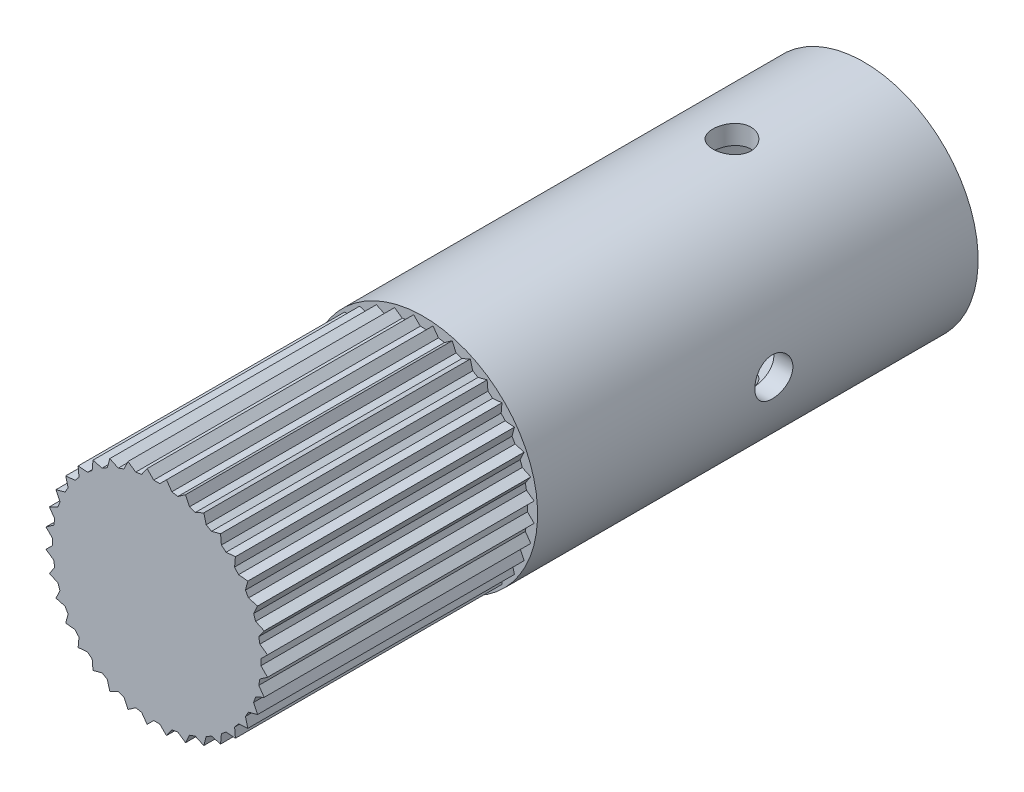
SolidWorks part; units mm, degrees
material "AISI 1015 Steel, Cold Drawn (SS)"
ref_plane "X-Y Datum" through (0, 0, 0) normal (0, 0, 1) x (1, 0, 0)
ref_plane "X-Z Datum" through (0, 0, 0) normal (0, 1, 0) x (1, 0, 0)
ref_plane "Y-Z Datum" through (0, 0, 0) normal (1, 0, 0) x (0, 0, -1)
sketch "Sketch9" plane through (0, 0, 0) normal (0, 1, 0) x (1, 0, 0)
  line L0 (16.002, 0) -> (0, 0)
  line L1 (0, 0) -> (0, -389.0916)
  line L2 (0, -389.0916) -> (-72.2493, -524.9728)
  dimension "D1" = 153.895
  dimension "D2" = 28
  dimension "D3" = 389.0916
  dimension "D5" = 16.002
sketch "Sketch5" plane through (0, 0, 0) normal (0, 1, 0) x (1, 0, 0)
  line L0 (7.9375, -81.1166) -> (7.9375, -22.1615)
  line L1 (7.9375, -22.1615) -> (9.525, -22.1615)
  line L2 (9.525, -22.1615) -> (9.525, -81.1166)
  line L3 (9.525, -81.1166) -> (7.9375, -81.1166)
  line L5 (16.002, 0) -> (0, 0) construction
  line L6 (0, 0) -> (0, -389.0916) construction
  line L7 (0, -389.0916) -> (9.525, -389.0916) construction
  line L8 (12.5602, -61.8666) -> (0, -61.8666) construction
  dimension "D1" = 1.5875
  dimension "D2" = 22.1615
  dimension "D3" = 7.9375
  dimension "D4" = 327.225
  dimension "D5" = 307.975
revolve "Revolve2" add sketch "Sketch5" angle 360 about L1
sketch "Sketch6" plane through (0, 0, 0) normal (0, 1, 0) x (1, 0, 0)
  circle A0 centre (0, -33.1635) radius 1.5875 construction
  circle A1 centre (0, -33.1635) radius 1.5875
sketch "Sketch7" plane through (0, 0, 0) normal (1, 0, 0) x (0, 0, -1)
  circle A2 centre (-39.196, 0) radius 1.5875
  circle A4 centre (-39.196, 0) radius 1.5875 construction
extrude "Cut-Extrude5" cut sketch "Sketch7" against normal through all both and the other way through all
extrude "Cut-Extrude6" cut sketch "Sketch6" against normal through all both and the other way through all
sketch "Sketch8" plane through (0, 0, 0) normal (0, 0, 1) x (1, 0, 0)
  line L0 (9.2357, -0.808) -> (8.6817, -0.254)
  line L1 (8.6817, -0.254) -> (8.6817, 0.254)
  line L2 (8.6817, 0.254) -> (9.2357, 0.808)
  line L3 (8.6817, 0) -> (0, 0) construction
  line L4 (8.9551, -2.3995) -> (8.5057, -1.7577)
  line L5 (8.5057, -1.7577) -> (8.5939, -1.2574)
  line L6 (8.5939, -1.2574) -> (9.2357, -0.808)
  line L7 (8.4024, -3.9181) -> (8.0713, -3.208)
  line L8 (8.0713, -3.208) -> (8.245, -2.7306)
  line L9 (8.245, -2.7306) -> (8.9551, -2.3995)
  line L10 (7.5944, -5.3176) -> (7.3916, -4.5608)
  line L11 (7.3916, -4.5608) -> (7.6456, -4.1209)
  line L12 (7.6456, -4.1209) -> (8.4024, -3.9181)
  line L13 (6.5556, -6.5556) -> (6.4873, -5.7751)
  line L14 (6.4873, -5.7751) -> (6.8138, -5.3859)
  line L15 (6.8138, -5.3859) -> (7.5944, -5.3176)
  line L16 (5.3176, -7.5944) -> (5.3859, -6.8138)
  line L17 (5.3859, -6.8138) -> (5.7751, -6.4873)
  line L18 (5.7751, -6.4873) -> (6.5556, -6.5556)
  line L19 (3.9181, -8.4024) -> (4.1209, -7.6456)
  line L20 (4.1209, -7.6456) -> (4.5608, -7.3916)
  line L21 (4.5608, -7.3916) -> (5.3176, -7.5944)
  line L22 (2.3995, -8.9551) -> (2.7306, -8.245)
  line L23 (2.7306, -8.245) -> (3.208, -8.0713)
  line L24 (3.208, -8.0713) -> (3.9181, -8.4024)
  line L25 (0.808, -9.2357) -> (1.2574, -8.5939)
  line L26 (1.2574, -8.5939) -> (1.7577, -8.5057)
  line L27 (1.7577, -8.5057) -> (2.3995, -8.9551)
  line L28 (-0.808, -9.2357) -> (-0.254, -8.6817)
  line L29 (-0.254, -8.6817) -> (0.254, -8.6817)
  line L30 (0.254, -8.6817) -> (0.808, -9.2357)
  line L31 (-2.3995, -8.9551) -> (-1.7577, -8.5057)
  line L32 (-1.7577, -8.5057) -> (-1.2574, -8.5939)
  line L33 (-1.2574, -8.5939) -> (-0.808, -9.2357)
  line L34 (-3.9181, -8.4024) -> (-3.208, -8.0713)
  line L35 (-3.208, -8.0713) -> (-2.7306, -8.245)
  line L36 (-2.7306, -8.245) -> (-2.3995, -8.9551)
  line L37 (-5.3176, -7.5944) -> (-4.5608, -7.3916)
  line L38 (-4.5608, -7.3916) -> (-4.1209, -7.6456)
  line L39 (-4.1209, -7.6456) -> (-3.9181, -8.4024)
  line L40 (-6.5556, -6.5556) -> (-5.7751, -6.4873)
  line L41 (-5.7751, -6.4873) -> (-5.3859, -6.8138)
  line L42 (-5.3859, -6.8138) -> (-5.3176, -7.5944)
  line L43 (-7.5944, -5.3176) -> (-6.8138, -5.3859)
  line L44 (-6.8138, -5.3859) -> (-6.4873, -5.7751)
  line L45 (-6.4873, -5.7751) -> (-6.5556, -6.5556)
  line L46 (-8.4024, -3.9181) -> (-7.6456, -4.1209)
  line L47 (-7.6456, -4.1209) -> (-7.3916, -4.5608)
  line L48 (-7.3916, -4.5608) -> (-7.5944, -5.3176)
  line L49 (-8.9551, -2.3995) -> (-8.245, -2.7306)
  line L50 (-8.245, -2.7306) -> (-8.0713, -3.208)
  line L51 (-8.0713, -3.208) -> (-8.4024, -3.9181)
  line L52 (-9.2357, -0.808) -> (-8.5939, -1.2574)
  line L53 (-8.5939, -1.2574) -> (-8.5057, -1.7577)
  line L54 (-8.5057, -1.7577) -> (-8.9551, -2.3995)
  line L55 (-9.2357, 0.808) -> (-8.6817, 0.254)
  line L56 (-8.6817, 0.254) -> (-8.6817, -0.254)
  line L57 (-8.6817, -0.254) -> (-9.2357, -0.808)
  line L58 (-8.9551, 2.3995) -> (-8.5057, 1.7577)
  line L59 (-8.5057, 1.7577) -> (-8.5939, 1.2574)
  line L60 (-8.5939, 1.2574) -> (-9.2357, 0.808)
  line L61 (-8.4024, 3.9181) -> (-8.0713, 3.208)
  line L62 (-8.0713, 3.208) -> (-8.245, 2.7306)
  line L63 (-8.245, 2.7306) -> (-8.9551, 2.3995)
  line L64 (-7.5944, 5.3176) -> (-7.3916, 4.5608)
  line L65 (-7.3916, 4.5608) -> (-7.6456, 4.1209)
  line L66 (-7.6456, 4.1209) -> (-8.4024, 3.9181)
  line L67 (-6.5556, 6.5556) -> (-6.4873, 5.7751)
  line L68 (-6.4873, 5.7751) -> (-6.8138, 5.3859)
  line L69 (-6.8138, 5.3859) -> (-7.5944, 5.3176)
  line L70 (-5.3176, 7.5944) -> (-5.3859, 6.8138)
  line L71 (-5.3859, 6.8138) -> (-5.7751, 6.4873)
  line L72 (-5.7751, 6.4873) -> (-6.5556, 6.5556)
  line L73 (-3.9181, 8.4024) -> (-4.1209, 7.6456)
  line L74 (-4.1209, 7.6456) -> (-4.5608, 7.3916)
  line L75 (-4.5608, 7.3916) -> (-5.3176, 7.5944)
  line L76 (-2.3995, 8.9551) -> (-2.7306, 8.245)
  line L77 (-2.7306, 8.245) -> (-3.208, 8.0713)
  line L78 (-3.208, 8.0713) -> (-3.9181, 8.4024)
  line L79 (-0.808, 9.2357) -> (-1.2574, 8.5939)
  line L80 (-1.2574, 8.5939) -> (-1.7577, 8.5057)
  line L81 (-1.7577, 8.5057) -> (-2.3995, 8.9551)
  line L82 (0.808, 9.2357) -> (0.254, 8.6817)
  line L83 (0.254, 8.6817) -> (-0.254, 8.6817)
  line L84 (-0.254, 8.6817) -> (-0.808, 9.2357)
  line L85 (2.3995, 8.9551) -> (1.7577, 8.5057)
  line L86 (1.7577, 8.5057) -> (1.2574, 8.5939)
  line L87 (1.2574, 8.5939) -> (0.808, 9.2357)
  line L88 (3.9181, 8.4024) -> (3.208, 8.0713)
  line L89 (3.208, 8.0713) -> (2.7306, 8.245)
  line L90 (2.7306, 8.245) -> (2.3995, 8.9551)
  line L91 (5.3176, 7.5944) -> (4.5608, 7.3916)
  line L92 (4.5608, 7.3916) -> (4.1209, 7.6456)
  line L93 (4.1209, 7.6456) -> (3.9181, 8.4024)
  line L94 (6.5556, 6.5556) -> (5.7751, 6.4873)
  line L95 (5.7751, 6.4873) -> (5.3859, 6.8138)
  line L96 (5.3859, 6.8138) -> (5.3176, 7.5944)
  line L97 (7.5944, 5.3176) -> (6.8138, 5.3859)
  line L98 (6.8138, 5.3859) -> (6.4873, 5.7751)
  line L99 (6.4873, 5.7751) -> (6.5556, 6.5556)
  line L100 (8.4024, 3.9181) -> (7.6456, 4.1209)
  line L101 (7.6456, 4.1209) -> (7.3916, 4.5608)
  line L102 (7.3916, 4.5608) -> (7.5944, 5.3176)
  line L103 (8.9551, 2.3995) -> (8.245, 2.7306)
  line L104 (8.245, 2.7306) -> (8.0713, 3.208)
  line L105 (8.0713, 3.208) -> (8.4024, 3.9181)
  line L106 (9.2357, 0.808) -> (8.5939, 1.2574)
  line L107 (8.5939, 1.2574) -> (8.5057, 1.7577)
  line L108 (8.5057, 1.7577) -> (8.9551, 2.3995)
  circle A0 centre (0, 0) radius 12.7
  circle A1 centre (0, 0) radius 9.271 construction
  circle A2 centre (0, 0) radius 8.6854 construction
  point P153 (0, 0)
  dimension "D1" = 25.4
  dimension "D4" = 18.542
  dimension "D6" = 17.3708
  dimension "D2" = 0.508
  dimension "D3" = 135
  dimension "D5" = 36
extrude "Cut-Extrude7" cut sketch "Sketch8" against normal blind 22.225 from surface starting at face at (-9.525, 0, 81.1166)
ref_plane "Plane1" through (0, 0, 47.5615) normal (0, 0, -1) x (-1, 0, 0)
sketch "Sketch10" plane through (0, 0, 47.5615) normal (0, 0, -1) x (-1, 0, 0)
  circle A0 centre (0, 0) radius 7.9375
  dimension "D1" = 15.875
extrude "Boss-Extrude1" add sketch "Sketch10" against normal up to surface (33.5551 mm away) up to face at (-7.9375, 0, 81.1166)
sketch "Sketch11" plane through (0, 0, 22.1615) normal (0, 0, -1) x (-1, 0, 0)
  line L0 (0, 9.525) -> (13.3548, 9.525) construction
  line L1 (0, 9.525) -> (0, 15.4312) construction
  line L2 (-9.525, 0) -> (-9.525, 9.1744) construction
  line L3 (-9.525, 0) -> (-16.674, 0) construction
  circle A0 centre (0, 0) radius 9.525 construction
  point P0 (0, 9.525)
  point P1 (-9.525, 0)
